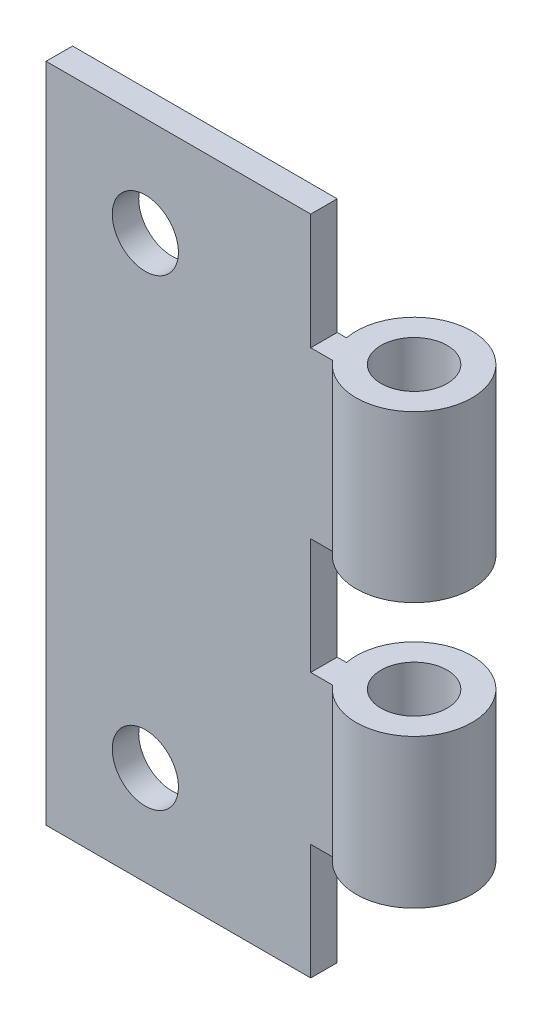
SolidWorks part; units mm, degrees
ref_plane "Front Plane" through (0, 0, 0) normal (0, 0, 1) x (1, 0, 0)
ref_plane "Top Plane" through (0, 0, 0) normal (0, 1, 0) x (1, 0, 0)
ref_plane "Right Plane" through (0, 0, 0) normal (1, 0, 0) x (0, 0, -1)
sketch "Sketch1" plane through (0, 0, 0) normal (0, 1, 0) x (1, 0, 0)
  line L0 (20.32, 2.032) -> (21.0323, 2.032)
  line L1 (0, 0) -> (20.32, 0)
  line L2 (0, 0) -> (0, 2.032)
  line L3 (0, 2.032) -> (20.32, 2.032)
  line L4 (20.32, 0) -> (20.32, 2.032)
  line L5 (20.32, 0) -> (21.9952, 0)
  circle A0 centre (25.4, 2.8575) radius 4.445
  dimension "D3" = 8.89
  dimension "D1" = 2.032
  dimension "D2" = 20.32
  dimension "D4" = 25.4
  dimension "D5" = 0.8255
extrude "Boss-Extrude1" add sketch "Sketch1" along normal blind 50.8 contours L1 L4 L3 L2 | A0 L0 L4 L5 | A0 region at (10.16, 0, -1.016) region at (20.8988, 0, -0.8684) region at (25.4, 0, -2.8575)
sketch "Sketch2" plane through (0, 0, -2.032) normal (0, 0, -1) x (-1, 0, 0)
  line L0 (0, 50.8) -> (-21.0323, 50.8) construction
  line L1 (0, 50.8) -> (0, 0) construction
  line L2 (0, 0) -> (-21.0323, 0) construction
  circle A0 centre (-7.62, 43.18) radius 2.54
  circle A1 centre (-7.62, 7.62) radius 2.54
  dimension "D1" = 5.08
  dimension "D4" = 5.08
  dimension "D2" = 7.62
  dimension "D3" = 7.62
  dimension "D5" = 7.62
  dimension "D6" = 7.62
extrude "Cut-Extrude1" cut sketch "Sketch2" against normal blind 50.8
extrude "Cut-Extrude2" cut sketch "Sketch1<3>" along normal blind 8.89 contours A0 L0 L4 L5 | A0 region at (20.8988, 0, -0.8684) region at (25.4, 0, -2.8575)
sketch "Sketch1<3>" plane through (0, 0, 0) normal (0, 1, 0) x (1, 0, 0) same geometry as "Sketch1"
extrude "Cut-Extrude3" cut sketch "Sketch1<5>" along normal blind 8.89 from offset 20.32 contours A0 | A0 L0 L4 L5 region at (20.8988, 0, -0.8684) region at (25.4, 0, -2.8575)
sketch "Sketch1<5>" plane through (0, 0, 0) normal (0, 1, 0) x (1, 0, 0) same geometry as "Sketch1"
sketch "Sketch3" plane through (0, 50.8, 0) normal (0, 1, 0) x (1, 0, 0)
  arc A0 (21.9952, 0) -> (21.0323, 2.032) centre (25.4, 2.8575) ccw construction
  arc A1 (21.9952, 0) -> (21.0323, 2.032) centre (25.4, 2.8575) ccw
  circle A2 centre (25.4, 2.8575) radius 2.54
  dimension "D1" = 5.08
extrude "Cut-Extrude4" cut sketch "Sketch3" against normal through all contours A2 region at (25.4, 50.8, -2.8575)
extrude "Cut-Extrude5" cut sketch "Sketch1<6>" against normal blind 8.89 from offset 50.8 contours A0 | A0 L0 L4 L5 region at (20.8988, 0, -0.8684) region at (25.4, 0, -2.8575)
sketch "Sketch1<6>" plane through (0, 0, 0) normal (0, 1, 0) x (1, 0, 0) same geometry as "Sketch1"
